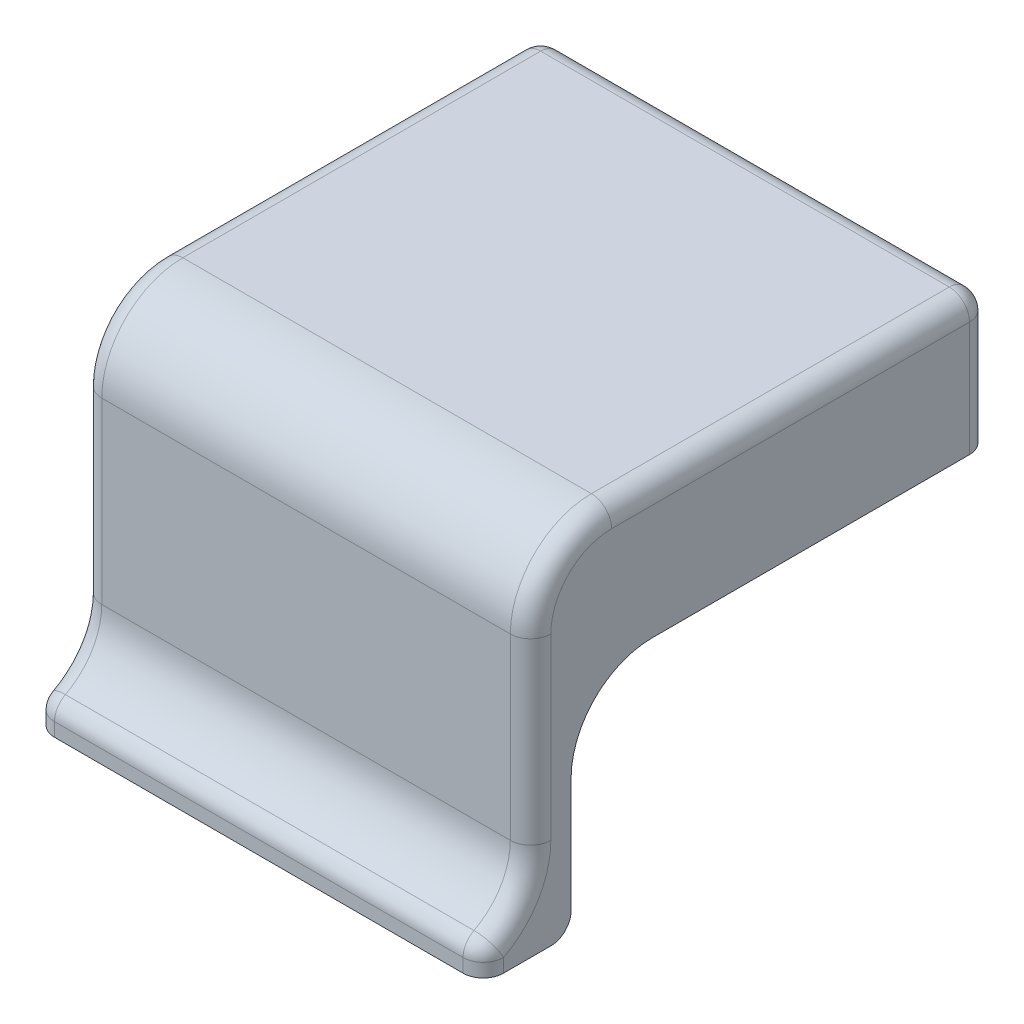
SolidWorks part; units mm, degrees
ref_plane "Front Plane" through (0, 0, 0) normal (0, 0, 1) x (1, 0, 0)
ref_plane "Top Plane" through (0, 0, 0) normal (0, 1, 0) x (1, 0, 0)
ref_plane "Right Plane" through (0, 0, 0) normal (1, 0, 0) x (0, 0, -1)
sketch "Sketch1" plane through (0, 0, 0) normal (0, 1, 0) x (1, 0, 0)
  line L0 (0, 0) -> (-43.5, 0)
  line L1 (-43.5, 0) -> (-43.5, -68)
  line L2 (-43.5, -68) -> (23, -68)
  line L3 (23, -68) -> (23, 0)
  line L6 (0, 0) -> (23, 0)
  dimension "D1" = 43.5
  dimension "D3" = 68
  dimension "D4" = 66.5
extrude "Boss-Extrude1" add sketch "Sketch1" along normal blind 10
sketch "Sketch2" plane through (0, 0, 0) normal (0, -1, 0) x (1, 0, 0)
  line L0 (-43.5, 68) -> (-43.5, 62)
  line L1 (-43.5, 0) -> (-43.5, 68) construction
  line L2 (-43.5, 62) -> (23, 62)
  line L3 (23, 68) -> (23, 0) construction
  line L4 (23, 62) -> (23, 68)
  line L5 (23, 68) -> (-43.5, 68)
  dimension "D1" = 6
extrude "Boss-Extrude2" add sketch "Sketch2" along normal blind 42
sketch "Sketch4" plane through (0, 0, 0) normal (0, -1, 0) x (1, 0, 0)
  line L0 (-43.5, 62) -> (-36, 62)
  line L1 (-43.5, 62) -> (23, 62) construction
  line L5 (-43.5, 0) -> (-43.5, 62)
  line L6 (23, 0) -> (23, 62)
  line L7 (23, 62) -> (15.5, 62)
  line L8 (-43.5, 62) -> (23, 62) construction
  line L13 (-36, 62) -> (-36, 7.5)
  line L14 (-36, 7.5) -> (15.5, 7.5)
  line L15 (15.5, 7.5) -> (15.5, 62)
  line L16 (-43.5, 0) -> (23, 0)
  dimension "D1" = 7.5
  dimension "D2" = 7.5
  dimension "D3" = 7.5
extrude "Boss-Extrude3" add sketch "Sketch4" along normal blind 10
sketch "Sketch3" plane through (0, 0, 0) normal (0, 0, -1) x (-1, 0, 0)
  line L0 (-23, 10) -> (43.5, 10) construction
  line L1 (43.5, 10) -> (43.5, -10) construction
  circle A0 centre (16, -22) radius 20.035
  dimension "D1" = 32
  dimension "D2" = 40.07
  dimension "D3" = 27.5
extrude "Cut-Extrude2" cut sketch "Sketch3" against normal blind 10
fillet "Fillet1" radius 12 1 edges at (19.25, -10, 62)
sketch "Sketch7" plane through (0, 0, 68) normal (0, 0, 1) x (1, 0, 0)
  line L0 (-43.5, -42) -> (23, -42)
  line L1 (23, -42) -> (23, -38)
  line L2 (23, 10) -> (23, -42) construction
  line L3 (23, -38) -> (-43.5, -38)
  line L4 (-43.5, 10) -> (-43.5, -42) construction
  line L5 (-43.5, -38) -> (-43.5, -42)
extrude "Boss-Extrude4" add sketch "Sketch7" along normal blind 7
sketch "Sketch8" plane through (0, -42, 0) normal (0, -1, 0) x (1, 0, 0)
  line L0 (23, 62) -> (23, 75) construction
  line L1 (-43.5, 75) -> (-43.5, 62) construction
  line L2 (-43.5, 75) -> (23, 75) construction
  circle A0 centre (-28.5, 67) radius 3.025
  circle A1 centre (3, 67) radius 3.025
  dimension "D1" = 6.05
  dimension "D2" = 6.05
  dimension "D3" = 20
  dimension "D4" = 15
  dimension "D5" = 8
extrude "Cut-Extrude3" cut sketch "Sketch8" against normal blind 3
fillet "Fillet2" radius 12 1 edges at (-10.25, 10, 68)
fillet "Fillet3" radius 10 1 edges at (-10.25, -38, 68)
fillet "Fillet4" radius 3 1 edges at (-10.25, -42, 62)
fillet "Fillet5" radius 3 14 edges at (23, -34.3767, 69.9377) (23, -15.2303, 68) (23, 6.4853, 64.4853) (-43.5, -34.3767, 69.9377) (-43.5, -15.2303, 68) (-43.5, 6.4853, 64.4853) (23, 10, 28) (23, 0, 0) (-10.25, 10, 0) (-43.5, 10, 28) (-43.5, 0, 0) (23, -40, 75) (-10.25, -38, 75) (-43.5, -40, 75)
